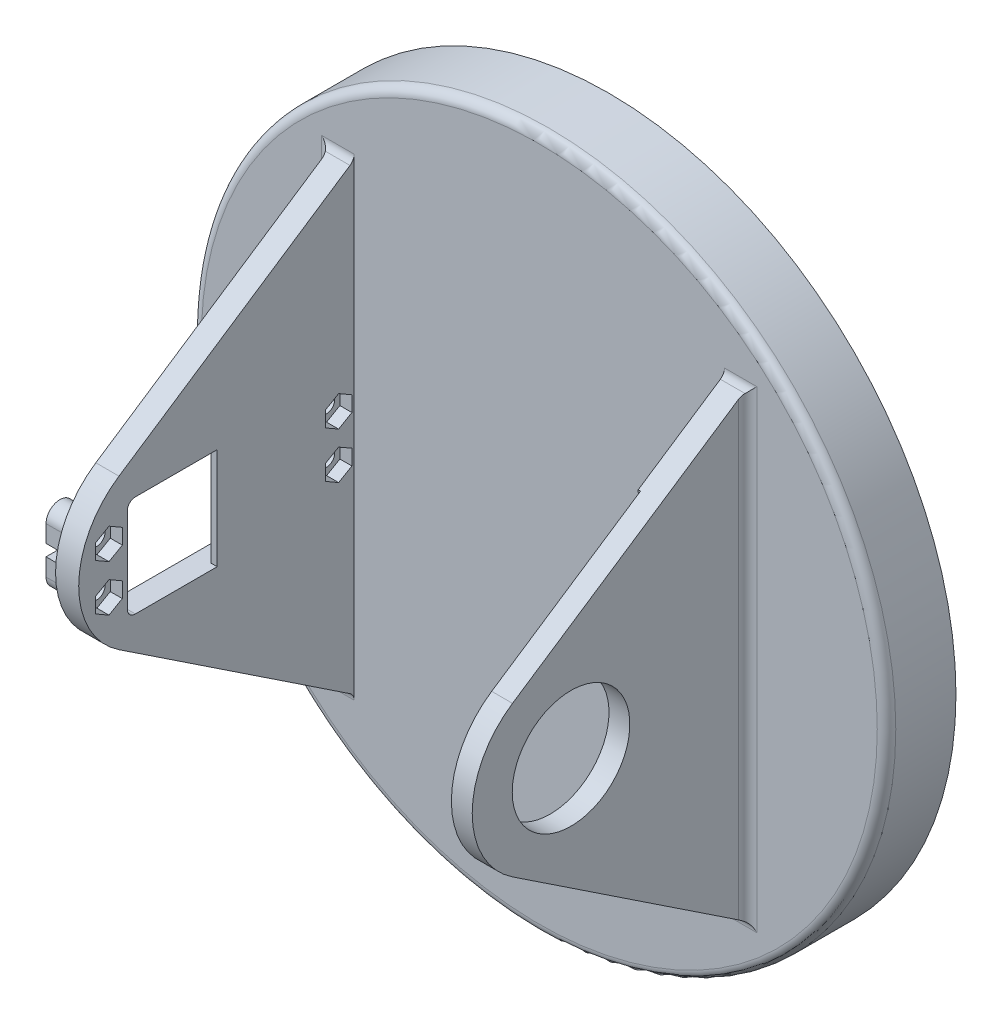
SolidWorks part; units mm, degrees
ref_plane "Front Plane" through (0, 0, 0) normal (0, 0, 1) x (1, 0, 0)
ref_plane "Top Plane" through (0, 0, 0) normal (0, 1, 0) x (1, 0, 0)
ref_plane "Right Plane" through (0, 0, 0) normal (1, 0, 0) x (0, 0, -1)
sketch "Sketch1" plane through (0, 0, 0) normal (0, 0, 1) x (1, 0, 0)
  circle A0 centre (0, 0) radius 75
  dimension "D1" = 150
extrude "Base Plate\\" add sketch "Sketch1" along normal blind 15
sketch "Sketch2" plane through (0, 0, 0) normal (0, 0, -1) x (-1, 0, 0)
  circle A0 centre (0, 0) radius 25 construction
  circle A1 centre (0, -25) radius 4.5
  circle A2 centre (-23.7764, -7.7254) radius 4.5
  circle A3 centre (-14.6946, 20.2254) radius 4.5
  circle A4 centre (14.6946, 20.2254) radius 4.5
  circle A5 centre (23.7764, -7.7254) radius 4.5
  point P16 (0, 0)
  dimension "D2" = 9
  dimension "D3" = 50
  dimension "D1" = 5
extrude "Drive Holes" cut sketch "Sketch2" against normal blind 10
chamfer "Chamfer1" distance 1 5 edges at (19.2764, -7.7254, 0) (10.1946, 20.2254, 0) (-19.1946, 20.2254, 0) (-28.2764, -7.7254, 0) (-4.5, -25, 0)
sketch "Sketch4" plane through (0, 0, 0) normal (1, 0, 0) x (0, 0, -1)
  line L0 (-15, 50) -> (-65.792, 16.2334)
  line L1 (-15, 75) -> (-15, -75) construction
  line L2 (-65.792, -16.2334) -> (-15, -50)
  line L3 (-15, -50) -> (-15, 50)
  arc A0 (-65.792, 16.2334) -> (-65.792, -16.2334) centre (-55, 0) ccw
  dimension "D1" = 100
  dimension "D2" = 40
extrude "Base Fin" add sketch "Sketch4" against normal blind 5 from offset 45
sketch "Sketch5" plane through (40, 0, 0) normal (-1, 0, 0) x (0, 0, 1)
  line L0 (15, 50) -> (15, -50)
  line L1 (15, -50) -> (65.792, -16.2334)
  line L2 (65.792, 16.2334) -> (15, 50)
  arc A0 (65.792, -16.2334) -> (65.792, 16.2334) centre (55, 0) ccw
extrude "Base Fin 2" add sketch "Sketch5" against normal blind 5 from offset 85
sketch "Sketch6" plane through (-45, 0, 0) normal (-1, 0, 0) x (0, 0, 1)
  line L0 (64, 8.8325) -> (64, -9.5675)
  line L1 (62.25, -11.3175) -> (24.05, -11.3175)
  line L2 (22.3, -9.5675) -> (22.3, 8.8325)
  line L3 (24.05, 10.5825) -> (62.25, 10.5825)
  arc A0 (64, -9.5675) -> (62.25, -11.3175) centre (62.25, -9.5675) cw
  arc A1 (24.05, -11.3175) -> (22.3, -9.5675) centre (24.05, -9.5675) cw
  arc A2 (22.3, 8.8325) -> (24.05, 10.5825) centre (24.05, 8.8325) cw
  arc A3 (62.25, 10.5825) -> (64, 8.8325) centre (62.25, 8.8325) cw
extrude "Cut-Extrude1" cut sketch "Sketch6" against normal up to next
sketch "Sketch7" plane through (-45, 0, 0) normal (-1, 0, 0) x (0, 0, 1)
  circle A0 centre (18.35, 4.6325) radius 1.75
  circle A1 centre (18.35, -5.3675) radius 1.75
  circle A2 centre (67.95, -5.3675) radius 1.75
  circle A3 centre (67.95, 4.6325) radius 1.75
  dimension "D1" = 3.5
extrude "Cut-Extrude2" cut sketch "Sketch7" against normal up to next
sketch "Sketch8" plane through (-45, 0, 0) normal (-1, 0, 0) x (0, 0, 1)
  line L0 (67.95, 4.6325) -> (67.95, -5.3675) construction
  line L1 (70.95, 4.6325) -> (70.95, -5.3675)
  line L2 (64.95, 4.6325) -> (64.95, -5.3675)
  line L3 (15, 7.6325) -> (15, 0)
  line L4 (15, -75) -> (15, 75) construction
  line L5 (15, 0) -> (15, -8.3675)
  line L6 (15, -8.3675) -> (18.35, -8.3675)
  line L7 (21.35, -5.3675) -> (21.35, 4.6325)
  line L8 (18.35, 7.6325) -> (15, 7.6325)
  arc A0 (70.95, 4.6325) -> (64.95, 4.6325) centre (67.95, 4.6325) ccw
  arc A1 (64.95, -5.3675) -> (70.95, -5.3675) centre (67.95, -5.3675) ccw
  arc A2 (18.35, -8.3675) -> (21.35, -5.3675) centre (18.35, -5.3675) ccw
  arc A3 (21.35, 4.6325) -> (18.35, 7.6325) centre (18.35, 4.6325) ccw
  circle A4 centre (18.35, 4.6325) radius 1.75 construction
  circle A5 centre (18.35, -5.3675) radius 1.75 construction
  point P4 (67.95, -0.3675)
  dimension "D1" = 3
  dimension "D2" = 3
extrude "Boss-Extrude1" add sketch "Sketch8" along normal up to surface (5.6 mm away)
sketch "Sketch9" plane through (-45, 0, 0) normal (1, 0, 0) x (0, 0, -1)
  circle A0 centre (-67.95, -5.3675) radius 1.75
  circle A1 centre (-67.95, 4.6325) radius 1.75
  circle A2 centre (-18.35, -5.3675) radius 1.75
  circle A3 centre (-18.35, 4.6325) radius 1.75
extrude "Cut-Extrude3" cut sketch "Sketch9" against normal up to surface (5.6 mm away) up to face at (-50.6, -0.3675, 18.4404)
sketch "Sketch10" plane through (-50.6, 0, 0) normal (-1, 0, 0) x (0, 0, 1)
  line L0 (21.35, 0.8825) -> (16.75, 0.8825)
  line L1 (21.35, 4.6325) -> (21.35, -5.3675) construction
  line L2 (16.75, 0.8825) -> (16.75, -1.6175)
  line L3 (16.75, -1.6175) -> (21.35, -1.6175)
  line L4 (23.05, 0.3825) -> (17.25, 0.3825) construction
  line L5 (17.25, -1.1175) -> (23.05, -1.1175) construction
  line L6 (17.25, 0.3825) -> (17.25, -1.1175) construction
  line L7 (21.35, 0.8825) -> (21.35, -1.6175)
  line L10 (64.95, -5.3675) -> (64.95, 4.6325) construction
  line L14 (64.95, -1.5747) -> (64.95, 0.9253)
  line L22 (64.95, 0.9253) -> (70.95, 0.9253)
  line L23 (70.95, 4.6325) -> (70.95, -5.3675) construction
  line L24 (70.95, 0.9253) -> (70.95, -1.5747)
  line L25 (70.95, -1.5747) -> (64.95, -1.5747)
  dimension "D1" = 0.5
  dimension "D2" = 0.5
  dimension "D3" = 0.5
extrude "Cut-Extrude4" cut sketch "Sketch10" against normal up to surface (5.6 mm away) up to face at (-45, -0.2205, 28.0928)
sketch "Sketch11" plane through (-40, 0, 0) normal (1, 0, 0) x (0, 0, -1)
  line L1 (-65.075, -7.0274) -> (-65.075, -3.7076)
  line L2 (-65.075, -3.7076) -> (-67.95, -2.0477)
  line L3 (-67.95, -2.0477) -> (-70.825, -3.7076)
  line L4 (-70.825, -3.7076) -> (-70.825, -7.0274)
  line L5 (-70.825, -7.0274) -> (-67.95, -8.6873)
  line L6 (-67.95, -8.6873) -> (-65.075, -7.0274)
  line L7 (-65.075, 2.9726) -> (-65.075, 6.2924)
  line L8 (-65.075, 6.2924) -> (-67.95, 7.9523)
  line L9 (-67.95, 7.9523) -> (-70.825, 6.2924)
  line L10 (-70.825, 6.2924) -> (-70.825, 2.9726)
  line L11 (-70.825, 2.9726) -> (-67.95, 1.3127)
  line L12 (-67.95, 1.3127) -> (-65.075, 2.9726)
  line L13 (-15.475, -7.0274) -> (-15.475, -3.7076)
  line L14 (-15.475, -3.7076) -> (-18.35, -2.0477)
  line L15 (-18.35, -2.0477) -> (-21.225, -3.7076)
  line L16 (-21.225, -3.7076) -> (-21.225, -7.0274)
  line L17 (-21.225, -7.0274) -> (-18.35, -8.6873)
  line L18 (-18.35, -8.6873) -> (-15.475, -7.0274)
  line L19 (-15.475, 2.9726) -> (-15.475, 6.2924)
  line L20 (-15.475, 6.2924) -> (-18.35, 7.9523)
  line L21 (-18.35, 7.9523) -> (-21.225, 6.2924)
  line L22 (-21.225, 6.2924) -> (-21.225, 2.9726)
  line L23 (-21.225, 2.9726) -> (-18.35, 1.3127)
  line L24 (-18.35, 1.3127) -> (-15.475, 2.9726)
  circle A0 centre (-67.95, -5.3675) radius 2.875 construction
  circle A1 centre (-67.95, 4.6325) radius 2.875 construction
  circle A2 centre (-18.35, -5.3675) radius 2.875 construction
  circle A3 centre (-18.35, 4.6325) radius 2.875 construction
  circle A4 centre (-18.35, 4.6325) radius 1.75 construction
  dimension "D1" = 5.75
extrude "Cut-Extrude5" cut sketch "Sketch11" against normal blind 2.6
sketch "Sketch12" plane through (-40, 0, 0) normal (1, 0, 0) x (0, 0, -1)
  line L0 (-44.5721, -11.3175) -> (-44.5721, 10.5825)
  line L1 (-62.25, -11.3175) -> (-24.05, -11.3175) construction
  line L2 (-24.05, 10.5825) -> (-62.25, 10.5825) construction
  line L3 (-44.5721, 10.5825) -> (-24.05, 10.5825)
  line L4 (-22.3, 8.8325) -> (-22.3, -9.5675)
  line L5 (-24.05, -11.3175) -> (-44.5721, -11.3175)
  arc A0 (-24.05, 10.5825) -> (-22.3, 8.8325) centre (-24.05, 8.8325) cw
  arc A1 (-22.3, -9.5675) -> (-24.05, -11.3175) centre (-24.05, -9.5675) cw
extrude "Boss-Extrude2" add sketch "Sketch12" against normal up to surface (1.38 mm away)
fillet "Fillet1" radius 2 9 edges at (42.5, -50, 15) (42.5, 50, 15) (45, 0, 15) (-47.8, 7.6325, 15) (-47.8, -8.3675, 15) (-42.5, -50, 15) (-42.5, 50, 15) (-45, -29.1838, 15) (-45, 28.8162, 15)
fillet "Fillet2" radius 2 1 edges at (75, 0, 15)
sketch "Sketch13" plane through (40, 0, 0) normal (-1, 0, 0) x (0, 0, 1)
  circle A0 centre (53.15, -0.3675) radius 12.7
  arc A1 (49.1227, 19.2228) -> (57.1773, -19.9578) centre (53.15, -0.3675) ccw construction
  dimension "D1" = 25.4
extrude "Cut-Extrude6" cut sketch "Sketch13" against normal up to next
sketch "Sketch14" plane through (40, 0, 0) normal (-1, 0, 0) x (0, 0, 1)
  line L1 (15.8928, 49.4065) -> (65.792, 16.2334) construction
  line L2 (33.6357, 37.6109) -> (32.6621, -38.2582)
  line L3 (65.792, -16.2334) -> (15.8928, -49.4065) construction
  line L4 (32.6621, -38.2582) -> (65.792, -16.2334)
  line L5 (65.792, 16.2334) -> (33.6357, 37.6109)
  arc A1 (65.792, -16.2334) -> (65.792, 16.2334) centre (55, 0) ccw
extrude "Cut-Extrude7" cut sketch "Sketch14" against normal blind 0.5
